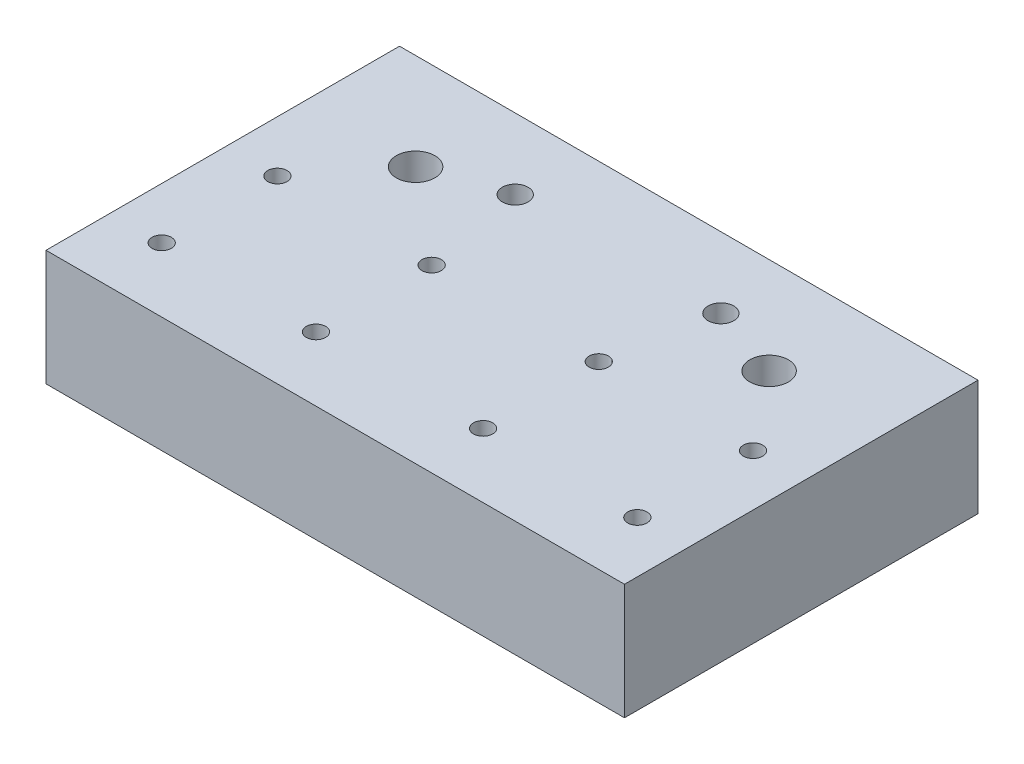
SolidWorks part; units mm, degrees
ref_plane "Front Plane" through (0, 0, 0) normal (0, 0, 1) x (1, 0, 0)
ref_plane "Top Plane" through (0, 0, 0) normal (0, 1, 0) x (1, 0, 0)
ref_plane "Right Plane" through (0, 0, 0) normal (1, 0, 0) x (0, 0, -1)
sketch "Sketch1" plane through (0, 0, 0) normal (0, 1, 0) x (1, 0, 0)
  line L0 (0, -383.892) -> (0, 18810.7071) construction
  line L1 (-45, 30) -> (45, 30)
  line L2 (-45, 30) -> (-45, -25)
  line L3 (-45, -25) -> (45, -25)
  line L4 (45, 30) -> (45, -25)
  line L7 (-383.892, 0) -> (18810.7071, 0) construction
  line L14 (25, -383.892) -> (25, 18810.7071) construction
  line L16 (13, -15) -> (37, -15) construction
  line L18 (13, -15) -> (13, 3) construction
  line L19 (13, 3) -> (37, 3) construction
  line L20 (37, -15) -> (37, 3) construction
  line L21 (13, -15) -> (37, 3) construction
  line L22 (13, 3) -> (37, -15) construction
  circle A0 centre (27.5, 15) radius 3
  circle A1 centre (-27.5, 15) radius 3
  circle A2 centre (37, 3) radius 1.5
  circle A3 centre (13, 3) radius 1.5
  circle A4 centre (37, -15) radius 1.5
  circle A5 centre (13, -15) radius 1.5
  circle A6 centre (-37, -15) radius 1.5
  circle A7 centre (-37, 3) radius 1.5
  circle A8 centre (-13, -15) radius 1.5
  circle A9 centre (-13, 3) radius 1.5
  point P0 (0, 0)
  point P11 (0, 0)
  point P19 (25, -6)
  dimension "D6" = 6
  dimension "D7" = 27.5
  dimension "D8" = 40
  dimension "D13" = 3
  dimension "D15" = 18
  dimension "D2" = 90
  dimension "D3" = 30
  dimension "D4" = 25
  dimension "D5" = 45
  dimension "D10" = 24
  dimension "D11" = 18
  dimension "D12" = 10
  dimension "D9" = 25
  dimension "D14" = 2
extrude "Boss-Extrude1" add sketch "Sketch1" along normal blind 18
sketch "Sketch2" plane through (0, 18, 0) normal (0, 1, 0) x (1, 0, 0)
  line L0 (45, -25) -> (45, 30) construction
  line L3 (0, -1000) -> (0, 49000) construction
  line L4 (45, 30) -> (-45, 30) construction
  circle A0 centre (16, 19) radius 2
  circle A3 centre (-16, 19) radius 2
  dimension "D1" = 11
  dimension "D2" = 4
  dimension "D3" = 29
extrude "Cut-Extrude1" cut sketch "Sketch2" against normal up to next
